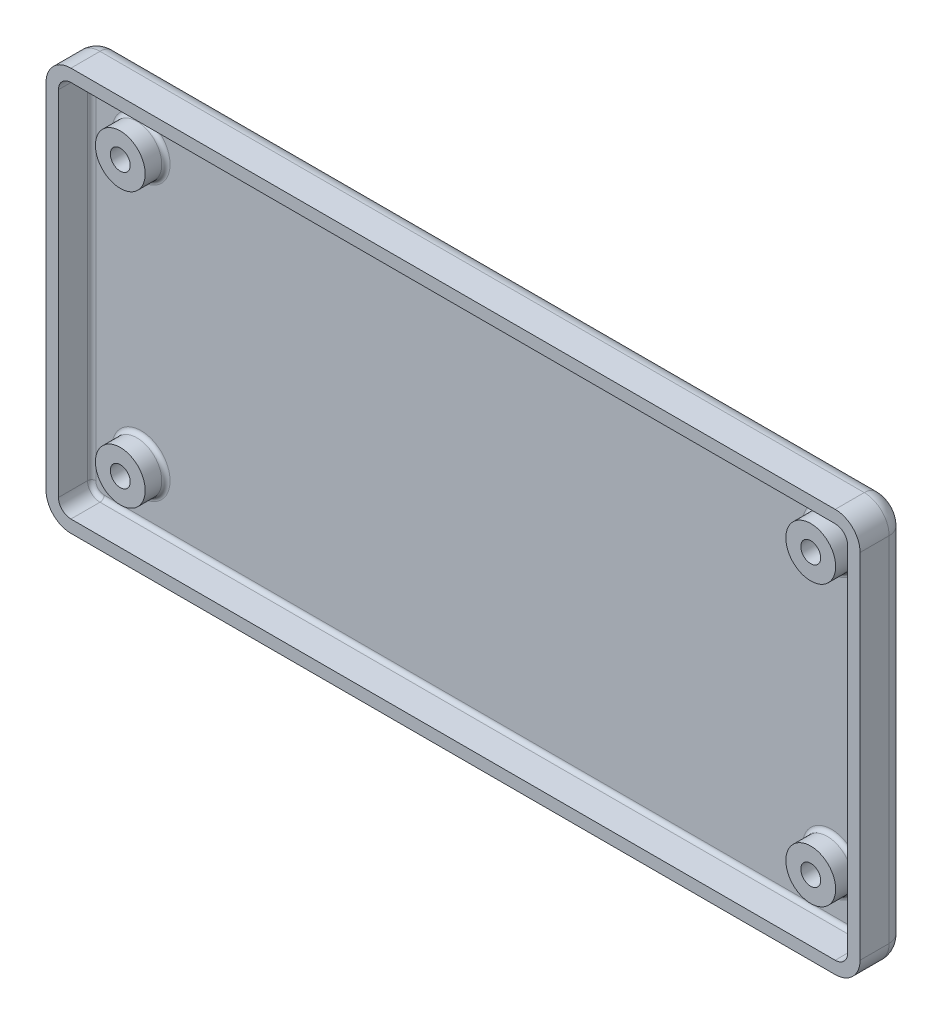
SolidWorks part; units mm, degrees
ref_plane "前视基准面" through (0, 0, 0) normal (0, 0, 1) x (1, 0, 0)
ref_plane "上视基准面" through (0, 0, 0) normal (0, 1, 0) x (1, 0, 0)
ref_plane "右视基准面" through (0, 0, 0) normal (1, 0, 0) x (0, 0, -1)
sketch "Sketch1" plane through (0, 0, 0) normal (0, 0, -1) x (-1, 0, 0)
  circle A0 centre (-153.035, -93.345) radius 3
  circle A1 centre (-153.035, -127) radius 3
  circle A2 centre (-69.85, -127) radius 3
  circle A3 centre (-69.85, -93.98) radius 3
  dimension "D1" = 6
extrude "Standoffs" add sketch "Sketch1" along normal blind 4
sketch "Sketch2" plane through (0, 0, -4) normal (0, 0, -1) x (-1, 0, 0)
  line L0 (-157.48, -88.9) -> (-65.405, -88.9) construction
  line L1 (-160.48, -85.9) -> (-62.405, -85.9)
  line L2 (-160.48, -85.9) -> (-160.48, -134.445)
  line L3 (-160.48, -134.445) -> (-62.405, -134.445)
  line L4 (-62.405, -85.9) -> (-62.405, -134.445)
  line L5 (-65.405, -131.445) -> (-157.48, -131.445) construction
  line L6 (-157.48, -131.445) -> (-157.48, -88.9) construction
  line L7 (-65.405, -88.9) -> (-65.405, -131.445) construction
  dimension "D1" = 3
  dimension "D2" = 3
  dimension "D3" = 3
  dimension "D4" = 3
extrude "Base" add sketch "Sketch2" against normal blind 1.5
sketch "Sketch5" plane through (0, 0, -2.5) normal (0, 0, 1) x (1, 0, 0)
  line L0 (158.98, -87.4) -> (63.905, -87.4)
  line L1 (63.905, -87.4) -> (63.905, -132.945)
  line L2 (63.905, -132.945) -> (158.98, -132.945)
  line L3 (158.98, -132.945) -> (158.98, -87.4)
  line L4 (160.48, -134.445) -> (160.48, -85.9)
  line L5 (160.48, -85.9) -> (62.405, -85.9)
  line L6 (62.405, -85.9) -> (62.405, -134.445)
  line L7 (62.405, -134.445) -> (160.48, -134.445)
  line L8 (160.48, -134.445) -> (160.48, -85.9)
  line L9 (160.48, -85.9) -> (62.405, -85.9)
  line L10 (62.405, -85.9) -> (62.405, -134.445)
  line L11 (62.405, -134.445) -> (160.48, -134.445)
  dimension "D1" = 0
  dimension "D2" = 1.5
extrude "Wall" add sketch "Sketch5" along normal blind 4
fillet "Fillet1" radius 3 4 edges at (62.405, -85.9, -1.25) (160.48, -85.9, -1.25) (160.48, -134.445, -1.25) (62.405, -134.445, -1.25)
fillet "Fillet2" radius 1.5 4 edges at (158.98, -87.4, -0.5) (158.98, -132.945, -0.5) (63.905, -132.945, -0.5) (63.905, -87.4, -0.5)
fillet "Fillet3" radius 2 8 edges at (159.6013, -133.5663, -4) (160.48, -110.1725, -4) (159.6013, -86.7787, -4) (111.4425, -85.9, -4) (63.2837, -86.7787, -4) (62.405, -110.1725, -4) (63.2837, -133.5663, -4) (111.4425, -134.445, -4)
fillet "Fillet4" radius 0.5 12 edges at (158.5407, -87.8393, -2.5) (158.98, -110.1725, -2.5) (158.5407, -132.5057, -2.5) (111.4425, -132.945, -2.5) (64.3443, -132.5057, -2.5) (63.905, -110.1725, -2.5) (64.3443, -87.8393, -2.5) (111.4425, -87.4, -2.5) (66.85, -93.98, -2.5) (150.035, -127, -2.5) (150.035, -93.345, -2.5) (66.85, -127, -2.5)
hole_wizard "CBORE for M2 Pan Head Machine Screw2" positions "Sketch9" profile "Sketch8" counterbore size "M2" standard "ANSI Metric" end condition through all
sketch "Sketch9" plane through (0, 0, -4) normal (0, 0, -1) x (-1, 0, 0)
  point P0 (-69.85, -93.98)
  point P2 (-153.035, -93.345)
  point P4 (-153.035, -127)
  point P6 (-69.85, -127)
sketch "Sketch8" plane through (69.85, -93.98, -4) normal (1, 0, 0) x (0, 1, 0)
  line L0 (0, 0) -> (0, 5.5)
  line L1 (0, 5.5) -> (1.2, 5.5)
  line L3 (1.2, 5.5) -> (1.2, 1.6)
  line L4 (1.2, 1.6) -> (2.5, 1.6)
  line L5 (2.5, 1.6) -> (2.5, 0)
  line L7 (2.5, 0) -> (0, 0)
  line L11 (0, -6.35) -> (0, 107.95) construction
  dimension "Thru Hole Dia." = 2.4
  dimension "Thru Hole Depth" = 5.5
  dimension "C'Bore Dia." = 5
  dimension "C'Bore Depth" = 1.6
